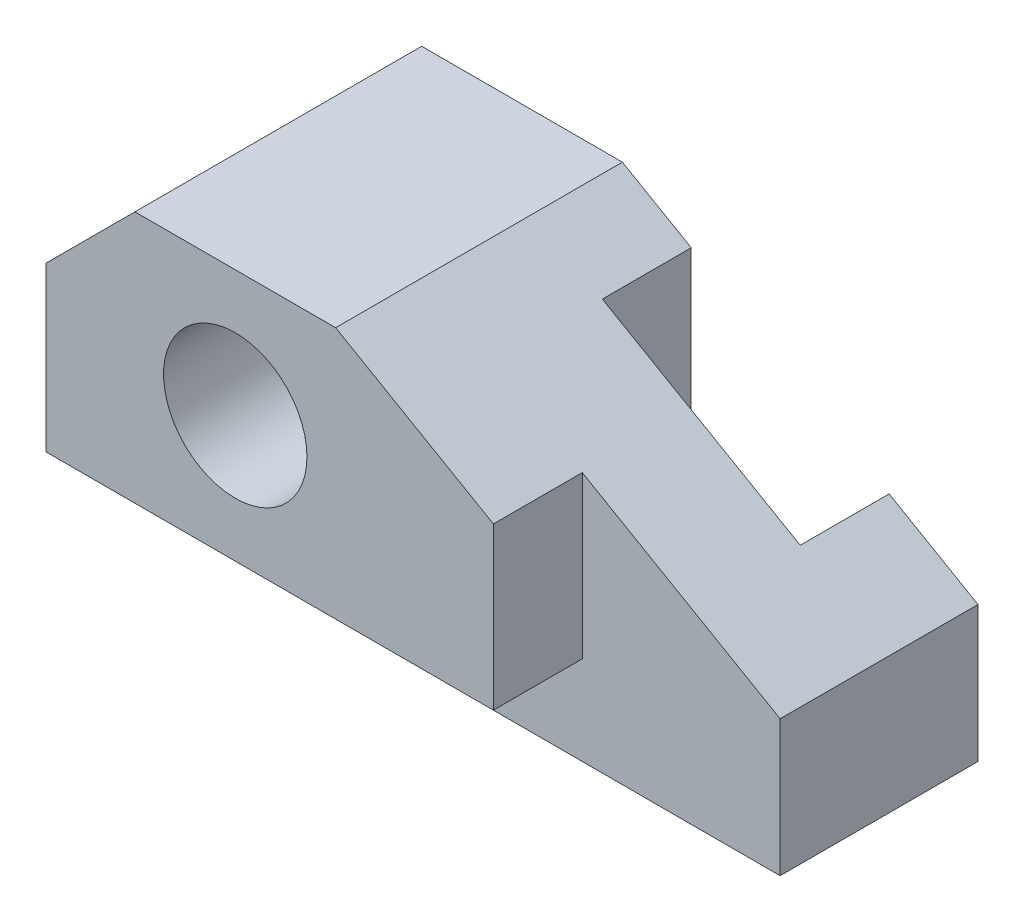
SolidWorks part; units mm, degrees
ref_plane "Front Plane" through (0, 0, 0) normal (0, 0, 1) x (1, 0, 0)
ref_plane "Top Plane" through (0, 0, 0) normal (0, 1, 0) x (1, 0, 0)
ref_plane "Right Plane" through (0, 0, 0) normal (1, 0, 0) x (0, 0, -1)
sketch "Sketch1" plane through (0, 0, 0) normal (0, 0, 1) x (1, 0, 0)
  line L0 (-33.528, 0) -> (80.772, 0)
  line L1 (80.772, 0) -> (80.772, 24.0836)
  line L2 (80.772, 24.0836) -> (17.78, 60.452)
  line L3 (17.78, 60.452) -> (-17.78, 60.452)
  line L4 (-17.78, 60.452) -> (-33.528, 44.704)
  line L5 (-33.528, 44.704) -> (-33.528, 0)
  line L6 (-33.528, 15.748) -> (45.72, 15.748)
  line L7 (45.72, 15.748) -> (45.72, 44.3208)
  circle A0 centre (0, 38.1) radius 12.7
  point P9 (0, 60.452)
  point P13 (0, 38.1)
  point P14 (56.4731, 15.748)
  point P15 (57.2467, 15.748)
  dimension "D8" = 25.4
  dimension "D1" = 114.3
  dimension "D2" = 15.748
  dimension "D3" = 45
  dimension "D4" = 35.56
  dimension "D5" = 30
  dimension "D6" = 15.748
  dimension "D7" = 60.452
  dimension "D9" = 38.1
  dimension "D10" = 35.052
extrude "Boss-Extrude1" add sketch "Sketch1" along normal mid plane 50.8 contours L6 L7 L2 L3 L4 L5 A0 | L7 L6 L5 L0 L1 L2 region at (33.2503, 12.6393, 0) region at (-32.6181, 30.226, 0)
extrude "Cut-Extrude1" cut sketch "Sketch1<4>" against normal blind 15.748 from offset 25.4 contours L7 L6 L5 L0 L1 L2 region at (33.2503, 12.6393, 0)
sketch "Sketch1<4>" plane through (0, 0, 0) normal (0, 0, 1) x (1, 0, 0) same geometry as "Sketch1"
sketch "Sketch2" plane through (0, 0, 0) normal (0, 1, 0) x (1, 0, 0)
  line L0 (29.972, 25.4) -> (29.972, 9.652)
  line L1 (80.772, 25.4) -> (17.78, 25.4) construction
  line L2 (29.972, 9.652) -> (65.024, 9.652)
  line L3 (65.024, 9.652) -> (65.024, 25.4)
  line L4 (65.024, 25.4) -> (29.972, 25.4)
  line L5 (80.772, -9.652) -> (80.772, 25.4) construction
  dimension "D1" = 35.052
  dimension "D2" = 15.748
  dimension "D3" = 15.748
extrude "Cut-Extrude2" cut sketch "Sketch2" against normal through all both and the other way through all
